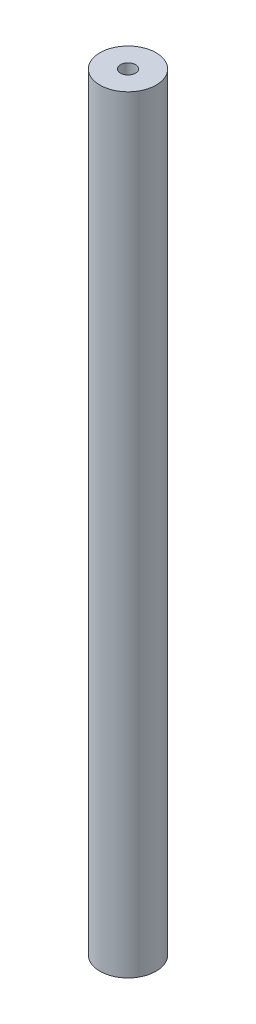
SolidWorks part; units mm, degrees
ref_plane "Front Plane" through (0, 0, 0) normal (0, 0, 1) x (1, 0, 0)
ref_plane "Top Plane" through (0, 0, 0) normal (0, 1, 0) x (1, 0, 0)
ref_plane "Right Plane" through (0, 0, 0) normal (1, 0, 0) x (0, 0, -1)
sketch "Sketch1" plane through (0, 0, 0) normal (0, 1, 0) x (1, 0, 0)
  circle A0 centre (0, 0) radius 7.5
  dimension "D1" = 15
extrude "Boss-Extrude1" add sketch "Sketch1" along normal mid plane 205
sketch "Sketch2" plane through (0, 102.5, 0) normal (0, 1, 0) x (1, 0, 0)
  circle A0 centre (0, 0) radius 2
  arc A1 (-2, -0.009) -> (2, 0.009) centre (0, 0) ccw construction
extrude "Cut-Extrude1" cut sketch "Sketch2" against normal blind 15
